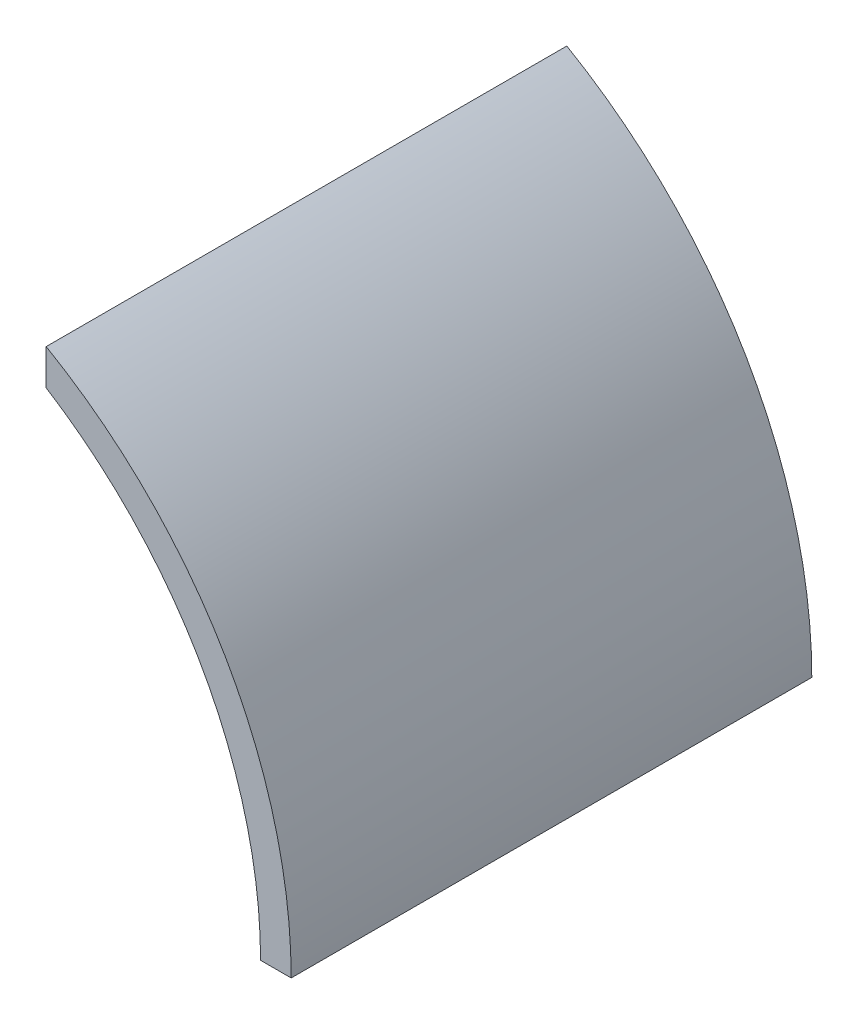
SolidWorks part; units mm, degrees
material "201 Annealed Stainless Steel (SS)"
ref_plane "Front Plane" through (0, 0, 0) normal (0, 0, 1) x (1, 0, 0)
ref_plane "Top Plane" through (0, 0, 0) normal (0, 1, 0) x (1, 0, 0)
ref_plane "Right Plane" through (0, 0, 0) normal (1, 0, 0) x (0, 0, -1)
sketch "Sketch2" plane through (0, 0, 0) normal (0, 0, 1) x (1, 0, 0)
  line L0 (-150, 0) -> (150, 0) construction
  line L1 (0, 150) -> (0, -160) construction
  line L2 (80, 0) -> (80, 108.9269) construction
  line L7 (80, 138.5641) -> (80, 126.8858)
  line L8 (0, -160) -> (0, -160.382) construction
  line L21 (150, 0) -> (160, 0)
  circle A0 centre (0, 0) radius 150 construction
  circle A1 centre (0, 0) radius 160 construction
  arc A2 (80, 126.8858) -> (150, 0) centre (0, 0) cw
  arc A3 (160, 0) -> (80, 138.5641) centre (0, 0) ccw
  point P5 (0, 150)
  point P10 (0, 0)
  point P11 (0, 0)
  point P13 (0, -160.382)
  point P15 (0, 0)
  point P16 (-150, 0)
  point P18 (0, 0)
  point P21 (0, 0)
  point P23 (0, 0)
  dimension "D1" = 300
  dimension "D2" = 320
  dimension "D3" = 80
extrude "Inner Ring - Right Side" add sketch "Sketch2" along normal blind 170
